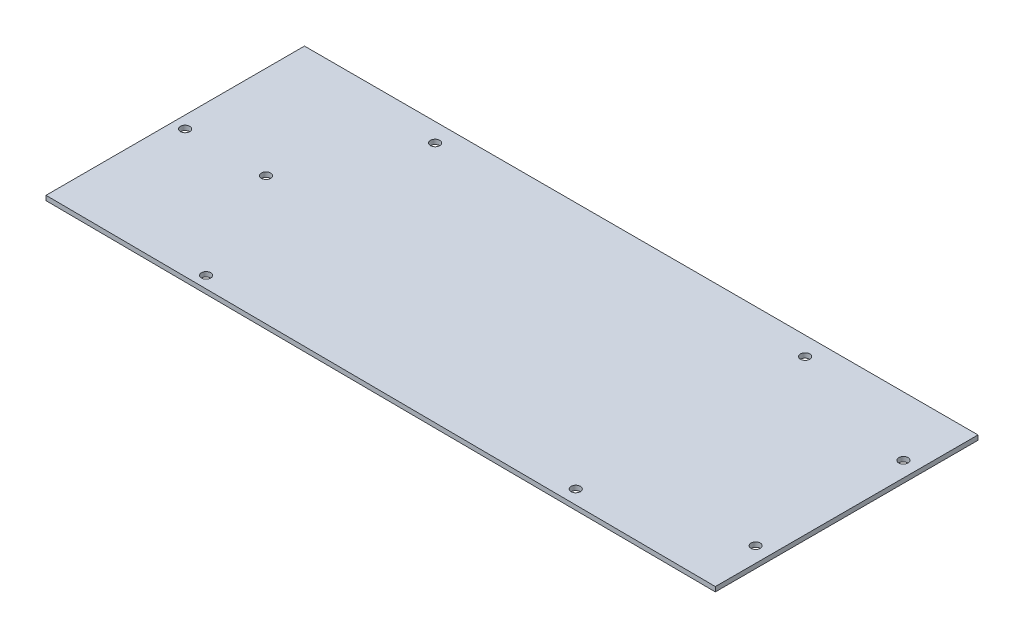
SolidWorks part; units mm, degrees
ref_plane "Front Plane" through (0, 0, 0) normal (0, 0, 1) x (1, 0, 0)
ref_plane "Top Plane" through (0, 0, 0) normal (0, 1, 0) x (1, 0, 0)
ref_plane "Right Plane" through (0, 0, 0) normal (1, 0, 0) x (0, 0, -1)
sketch "Sketch1" plane through (0, 0, 0) normal (0, 1, 0) x (1, 0, 0)
  line L6 (489.2758, -599.7266) -> (489.2758, -563.091)
  line L13 (56.0007, -497.9804) -> (489.2758, -497.9804)
  line L21 (56.0007, -664.2568) -> (489.2758, -666.9459)
  line L22 (489.2758, -497.9804) -> (489.2758, -563.091)
  line L36 (489.2758, -599.7266) -> (489.2758, -666.9459)
  line L38 (56.0007, -497.9804) -> (56.0007, -664.2568)
  circle A12 centre (63.7956, -582.5636) radius 3
  circle A13 centre (115.8464, -582.5636) radius 3
  circle A14 centre (152.0145, -509.9557) radius 3
  circle A15 centre (152.1131, -657.3773) radius 3
  circle A16 centre (390.0145, -657.4936) radius 3
  circle A17 centre (479.4749, -631.2236) radius 3
  circle A18 centre (479.4225, -536.1177) radius 3
  circle A19 centre (390.0145, -509.9557) radius 3
  point P4 (0, 0)
  point P5 (272.5206, -582.4819)
  dimension "D9" = 8.8361
  dimension "D12" = 9.8009
  dimension "D15" = 11.9753
  dimension "D16" = 99.2613
  dimension "D18" = 6
  dimension "D6" = 84.5832
  dimension "D17" = 6
  dimension "D21" = 6
  dimension "D22" = 6
  dimension "D23" = 6
  dimension "D24" = 6
  dimension "D4" = 11.9753
  dimension "D10" = 99.2613
  dimension "D11" = 35.6608
  dimension "D13" = 9.8533
  dimension "D14" = 38.1373
extrude "Boss-Extrude1" add sketch "Sketch1" along normal blind 3
